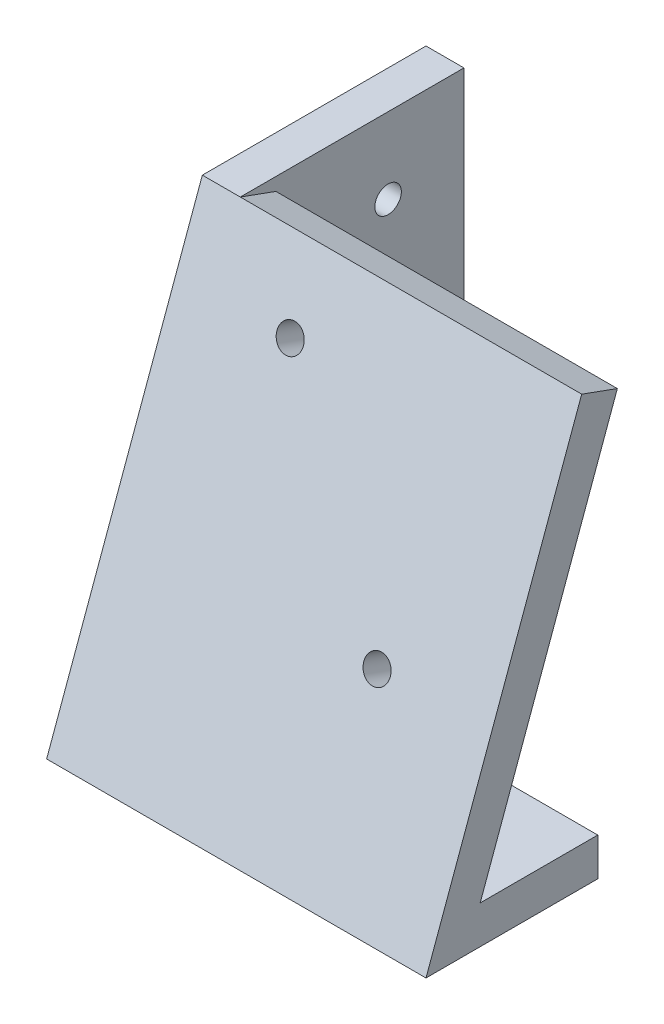
SolidWorks part; units mm, degrees
material "ABS"
ref_plane "Front Plane" through (0, 0, 0) normal (0, 0, 1) x (1, 0, 0)
ref_plane "Top Plane" through (0, 0, 0) normal (0, 1, 0) x (1, 0, 0)
ref_plane "Right Plane" through (0, 0, 0) normal (1, 0, 0) x (0, 0, -1)
sketch "Sketch1" plane through (0, 0, 0) normal (1, 0, 0) x (0, 0, -1)
  line L0 (0, 0) -> (-50, 0)
  line L1 (-50, 0) -> (-29.4788, 56.3816)
  line L2 (-29.4788, 56.3816) -> (-24.7803, 54.6715)
  line L3 (-24.7803, 54.6715) -> (-42.8593, 5)
  line L4 (-42.8593, 5) -> (0, 5)
  line L5 (0, 5) -> (0, 0)
  dimension "D1" = 60
  dimension "D2" = 50
  dimension "D3" = 70
  dimension "D4" = 5
  dimension "D5" = 5
extrude "Main" add sketch "Sketch1" along normal mid plane 50
sketch "Sketch2" plane through (0, 0, 0) normal (0, 0, -1) x (-1, 0, 0)
  line L0 (-25, 56.3816) -> (25, 56.3816) construction
  line L1 (-25, 0) -> (-20, 0)
  line L2 (-25, 0) -> (-25, 56.3816)
  line L3 (-25, 56.3816) -> (-20, 56.3816)
  line L4 (-20, 0) -> (-20, 56.3816)
  dimension "D1" = 5
extrude "Back" add sketch "Sketch2" against normal up to next
hole_wizard "Base Holes" positions "3DSketch4" profile "Sketch5" hole size "Ø3.5" standard "ANSI Metric"
sketch3d "3DSketch4"
  line L0 (-25, 5, 0) -> (-25, 5, 42.8593) construction
  line L4 (20, 5, 42.8593) -> (-25, 5, 42.8593) construction
  point P0 (10, 5, 32.6993)
  point P2 (-10, 5, 32.6993)
  dimension "D1" = 15
  dimension "D2" = 15
  dimension "D3" = 10.16
  dimension "D4" = 10.16
sketch "Sketch5" plane through (10, 5, 32.6993) normal (1, 0, 0) x (0, 0, 1)
  line L0 (0, 0) -> (0, 5)
  line L1 (0, 5) -> (1.75, 5)
  line L2 (1.75, 5) -> (1.75, 0)
  line L5 (1.75, 0) -> (0, 0)
  line L10 (0, 5) -> (-1.75, 5) construction
  line L11 (0, -6.35) -> (0, 107.95) construction
  dimension "Hole Dia." = 3.5
  dimension "Hole Depth" = 5
  dimension "Drill Angle" = 180
hole_wizard "BackPanelHoles" positions "Sketch6" profile "Sketch7" hole size "Ø1.0" standard "ANSI Metric"
sketch "Sketch6" plane through (20, 0, 0) normal (-1, 0, 0) x (0, 0, 1)
  line L0 (29.4788, 56.3816) -> (0, 56.3816) construction
  line L1 (0, 5) -> (0, 56.3816) construction
  line L2 (50, 0) -> (0, 0) construction
  point P0 (10, 46.3816)
  point P2 (25, 20)
  dimension "D1" = 10
  dimension "D2" = 10
  dimension "D3" = 20
  dimension "D4" = 25
sketch "Sketch7" plane through (20, 46.3816, 10) normal (0, 1, 0) x (0, 0, 1)
  line L0 (0, 0) -> (0, 5)
  line L1 (0, 5) -> (1.75, 5)
  line L2 (1.75, 5) -> (1.75, 0)
  line L5 (1.75, 0) -> (0, 0)
  line L10 (0, 5) -> (-1.75, 5) construction
  line L11 (0, -6.35) -> (0, 107.95) construction
  dimension "Hole Dia." = 3.5
  dimension "Hole Depth" = 5
  dimension "Drill Angle" = 180
hole_wizard "Ø1.0mm Dowel Hole1" positions "3DSketch5" profile "Sketch8" hole size "Ø1.0" standard "ANSI Metric"
sketch3d "3DSketch5"
  line L1 (20, 56.3816, 29.4788) -> (-25, 56.3816, 29.4788) construction
  line L2 (25, 0, 50) -> (-25, 0, 50) construction
  line L3 (-25, 56.3816, 29.4788) -> (-25, 0, 50) construction
  line L4 (25, 56.3816, 29.4788) -> (25, 0, 50) construction
  point P0 (-10, 46.9846, 32.899)
  point P2 (10, 23.4923, 41.4495)
  dimension "D1" = 15
  dimension "D2" = 10
  dimension "D3" = 25
  dimension "D4" = 15
sketch "Sketch8" plane through (-10, 46.9846, 32.899) normal (1, 0, 0) x (0, -0.9397, 0.342)
  line L0 (0, 0) -> (0, 5)
  line L1 (0, 5) -> (1.75, 5)
  line L2 (1.75, 5) -> (1.75, 0)
  line L5 (1.75, 0) -> (0, 0)
  line L10 (0, 5) -> (-1.75, 5) construction
  line L11 (0, -6.35) -> (0, 107.95) construction
  dimension "Hole Dia." = 3.5
  dimension "Hole Depth" = 5
  dimension "Drill Angle" = 180
ref_plane "Midplane" through (0, 0, 0) normal (-1, 0, 0) x (0, 0, 1)
mirror "Mirror1" about plane through (0, 0, 0) normal (-1, 0, 0) of "BackPanelHoles", "Back"
sketch "Sketch9" plane through (20, 0, 0) normal (-1, 0, 0) x (0, 0, 1)
  line L0 (29.4788, 56.3816) -> (0, 56.3816)
  line L1 (0, 56.3816) -> (0, 5)
  line L2 (0, 5) -> (42.8593, 5)
  line L3 (42.8593, 5) -> (24.7803, 54.6715)
  line L4 (24.7803, 54.6715) -> (29.4788, 56.3816)
extrude "Mirror Cut" cut sketch "Sketch9" against normal up to next
sketch "Sketch10" plane through (0, 5, 0) normal (0, 1, 0) x (1, 0, 0)
  line L0 (25, -42.8593) -> (25, 0) construction
  line L1 (-20, 0) -> (25, 0)
  line L2 (-20, 0) -> (-20, -5)
  line L3 (-20, -5) -> (25, -5)
  line L4 (25, 0) -> (25, -5)
  dimension "D1" = 5
extrude "BatteryCut" cut sketch "Sketch10" against normal up to next
sketch "Sketch11" plane through (0, 5, 0) normal (0, 1, 0) x (1, 0, 0)
  line L0 (-20, -5) -> (25, -5) construction
  line L1 (-8.3622, -5) -> (25, -5)
  line L2 (-8.3622, -5) -> (-8.3622, -27.3622)
  line L3 (-8.3622, -27.3622) -> (25, -27.3622)
  line L4 (25, -5) -> (25, -27.3622)
  line L5 (2.6378, -27.3622) -> (-7.3622, -27.3622) construction
  line L6 (-7.3622, -27.3622) -> (-7.3622, -12.3622) construction
  line L8 (25, -42.8593) -> (25, -5) construction
  dimension "D1" = 1
extrude "Cut-Extrude1" cut sketch "Sketch11" against normal through all
